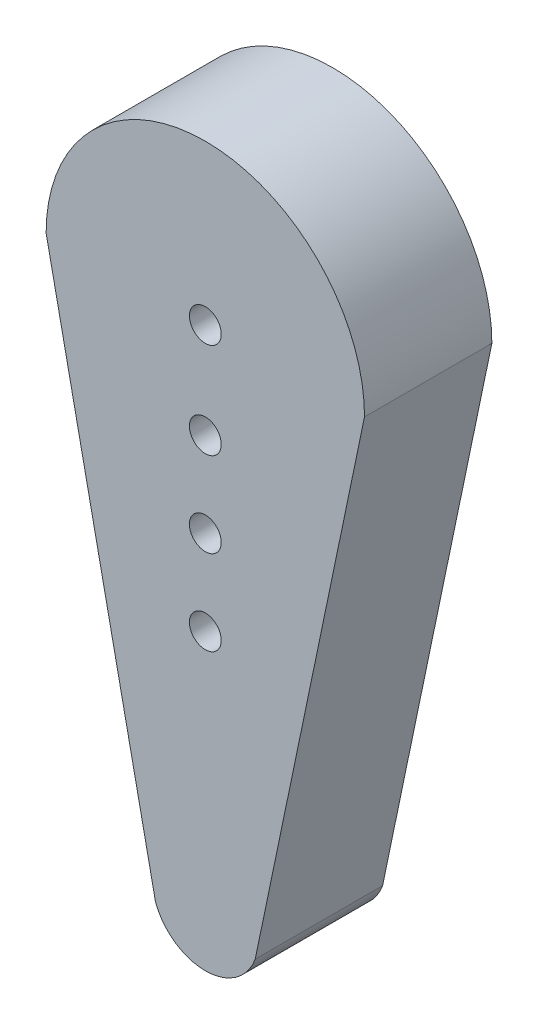
SolidWorks part; units mm, degrees
ref_plane "Front Plane" through (0, 0, 0) normal (0, 0, 1) x (1, 0, 0)
ref_plane "Top Plane" through (0, 0, 0) normal (0, 1, 0) x (1, 0, 0)
ref_plane "Right Plane" through (0, 0, 0) normal (1, 0, 0) x (0, 0, -1)
sketch "Sketch2" plane through (0, 0, 0) normal (0, 0, 1) x (1, 0, 0)
  line L0 (0, -55) -> (0, 55) construction
  line L1 (-7.5, 0) -> (-2.3473, -24.7102)
  line L2 (7.5, 0) -> (2.3504, -24.7019)
  arc A0 (7.5, 0) -> (-7.5, 0) centre (0, 0) ccw
  arc A1 (-2.3473, -24.7102) -> (2.3504, -24.7019) centre (0, -23.85) ccw
  point P1 (0, 0)
  point P3 (0, 0)
  point P11 (-2.3473, -24.7102)
  point P12 (2.175, -25.0826)
  point P13 (0, 0)
  point P14 (2.5, -23.85)
  point P15 (0, 0)
  point P16 (0, 0)
  point P17 (2.3504, -24.7102)
  dimension "D1" = 15
  dimension "D2" = 5
  dimension "D3" = 26.35
extrude "Boss-Extrude1" add sketch "Sketch2" along normal blind 6
sketch "Sketch3" plane through (0, 0, 0) normal (0, 0, 1) x (1, 0, 0)
  line L0 (-3.75, 0) -> (-2.25, -15)
  line L1 (2.25, -15) -> (3.75, 0)
  line L2 (0, -1.65) -> (0, 1.65) construction
  arc A0 (3.75, 0) -> (-3.75, 0) centre (0, 0) ccw
  arc A1 (-2.25, -15) -> (2.25, -15) centre (0, -15) ccw
  dimension "D1" = 7.5
  dimension "D2" = 4.5
  dimension "D3" = 15
extrude "Cut-Extrude3" cut sketch "Sketch3" along normal blind 4.7
sketch "Sketch4" plane through (0, 0, 4.7) normal (0, 0, -1) x (-1, 0, 0)
  circle A0 centre (0, 0) radius 0.75
  dimension "D1" = 1.5
extrude "Cut-Extrude4" cut sketch "Sketch4" against normal through all both and the other way through all
sketch "Sketch6" plane through (0, 0, 4.7) normal (0, 0, -1) x (-1, 0, 0)
  line L0 (0, 55) -> (0, -55) construction
  line L1 (55, 0) -> (-55, 0) construction
  circle A0 centre (0, -4.5) radius 0.75
  dimension "D1" = 1.5
  dimension "D2" = 4.5
extrude "Cut-Extrude6" cut sketch "Sketch6" against normal through all both and the other way through all
pattern_linear "LPattern1" count 3 spacing 4 along (0, -1, 0) of "Cut-Extrude6"
